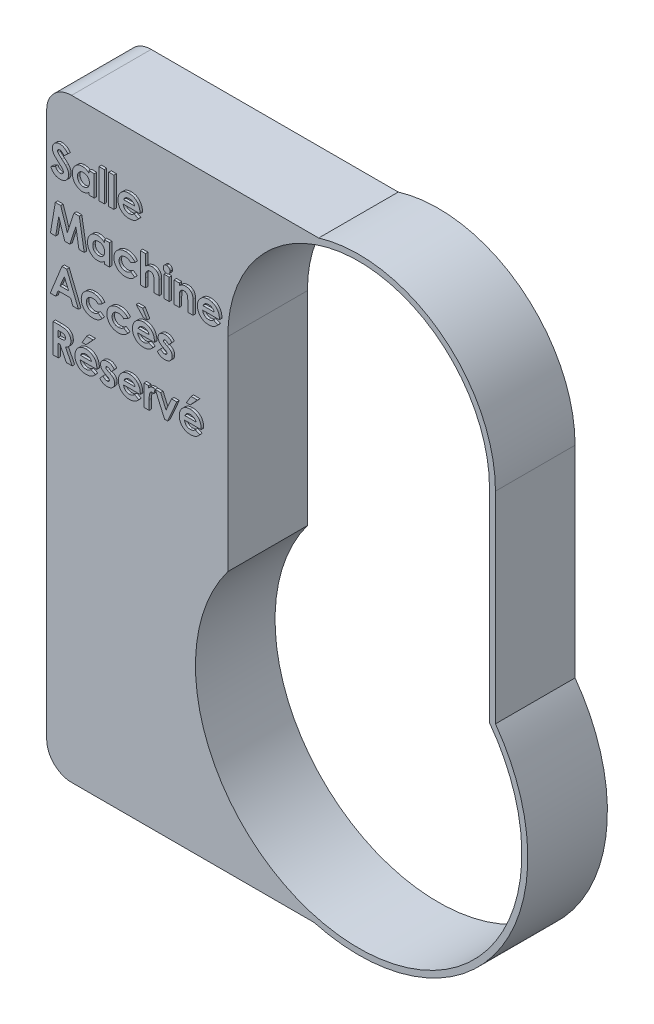
SolidWorks part; units mm, degrees
ref_plane "Plan de face" through (0, 0, 0) normal (0, 0, 1) x (1, 0, 0)
ref_plane "Plan de dessus" through (0, 0, 0) normal (0, 1, 0) x (1, 0, 0)
ref_plane "Plan de droite" through (0, 0, 0) normal (1, 0, 0) x (0, 0, -1)
sketch "Esquisse1" plane through (0, 0, 0) normal (0, 0, 1) x (1, 0, 0)
  line L0 (-26.3, -40.9003) -> (-26.3, 0)
  line L1 (26.3, 0) -> (26.3, -40.9003)
  line L2 (0, 26.3) -> (0, -93.3) construction
  arc A0 (-26.3, 0) -> (26.3, 0) centre (0, 0) cw
  arc A2 (-26.3, -40.9003) -> (26.3, -40.9003) centre (0, -60.5) ccw
  dimension "D2" = 65.6
  dimension "D1" = 52.6
  dimension "D3" = 119.6
extrude "Extru.-Mince1" add sketch "Esquisse1" along normal blind 16 thin thin type one direction wall 1.2
sketch "Esquisse2" plane through (0, 0, 0) normal (0, 0, 1) x (1, 0, 0)
  line L0 (0, 26.3) -> (-62.7, 26.3)
  line L1 (0, -93.3) -> (-62.7, -93.3)
  line L2 (-62.7, -93.3) -> (-62.7, 26.3)
  line L3 (26.3, -40.9003) -> (26.3, 0) construction
  line L4 (-26.3, -40.9003) -> (-26.3, 0)
  arc A0 (26.3, 0) -> (-26.3, 0) centre (0, 0) ccw construction
  arc A1 (-26.3, -40.9003) -> (26.3, -40.9003) centre (0, -60.5) ccw construction
  arc A2 (-26.3, 0) -> (0, 26.3) centre (0, 0) cw
  arc A3 (0, -93.3) -> (-26.3, -40.9003) centre (0, -60.5) cw
  point P18 (-62.7, 26.3)
  dimension "D1" = 89
extrude "Boss.-Extru.1" add sketch "Esquisse2" along normal blind 16
fillet "Congé1" radius 5 2 edges at (-62.7, 26.3, 8) (-62.7, -93.3, 8)
sketch "Esquisse3" plane through (0, 0, 16) normal (0, 0, 1) x (1, 0, 0)
  text T0 "<b>Salle</b>\r\n<b>Machine</b>\r\n<b>Accès </b>\r\n<b>Réservé</b>" font "Century Gothic" height in points 22
extrude "Enlèv. mat.-Extru.3" cut sketch "Esquisse3" against normal mid plane 1
extrude "Boss.-Extru.3" add sketch "Esquisse3<3>" along normal mid plane 1 separate body
sketch "Esquisse3<3>" plane through (0, 0, 16) normal (0, 0, 1) x (1, 0, 0) same geometry as "Esquisse3"
